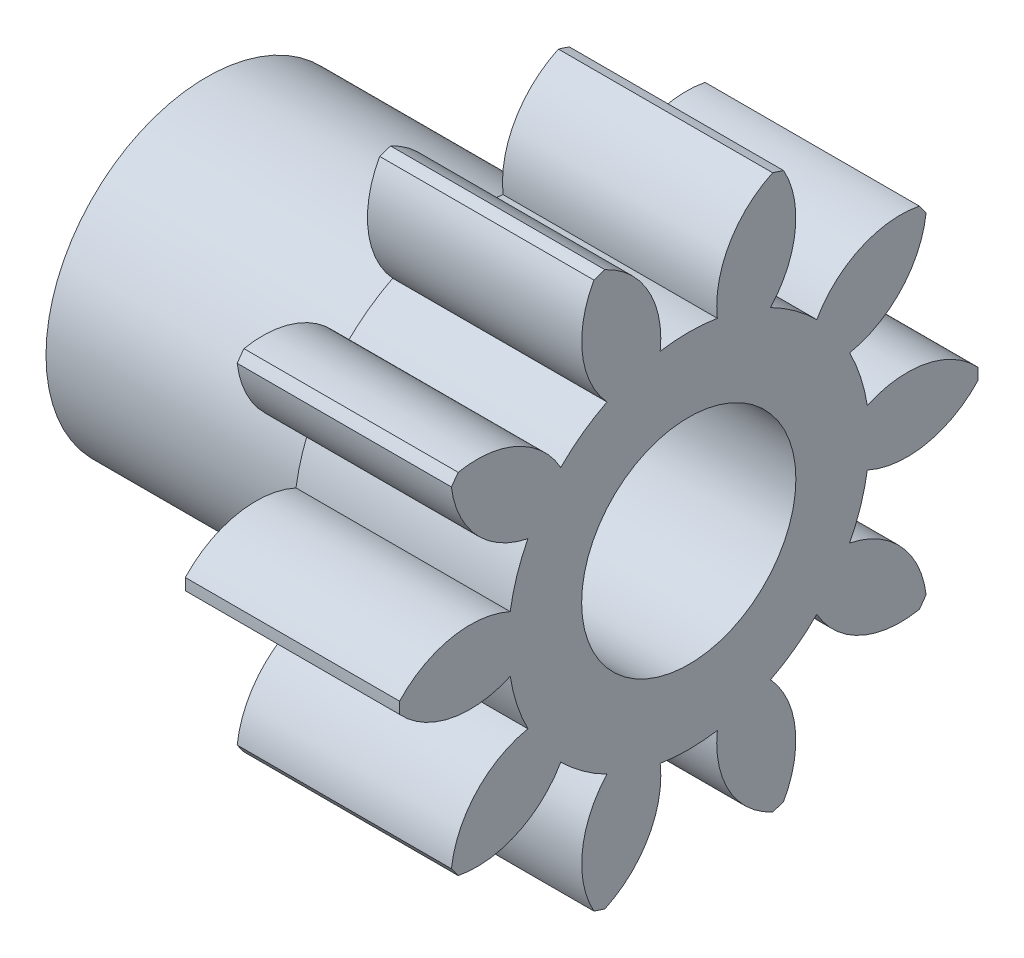
SolidWorks part; units mm, degrees
note: The reader was unsure of these and kept them because the rebuilt part matched: shared geometry of "Sketch8<2>".
ref_plane "Plane1" through (0, 0, 0) normal (0, 0, 1) x (1, 0, 0)
ref_plane "Plane2" through (0, 0, 0) normal (0, 1, 0) x (1, 0, 0)
ref_plane "Plane3" through (0, 0, 0) normal (1, 0, 0) x (0, 0, -1)
sketch "HoldingSke" plane through (0, 0, 0) normal (0, 1, 0) x (1, 0, 0)
  line L0 (0, 0) -> (1.0942, -0.1929)
  line L1 (-15, 0) -> (100, 0) construction
  line L2 (0, 0) -> (-2.1039, 2.3779)
  line L3 (0, 0) -> (-11.863, 4.5341)
  line L4 (0, 0) -> (8.5048, 1.4996)
  line L5 (0, 0) -> (-8.4326, -3.1451)
  line L6 (0, 0) -> (-3.3159, -2.2372)
  line L7 (-2.1039, 2.3779) -> (-0.1666, 11.167)
  line L8 (-76.2, 54.61) -> (-75.5, 54.61)
  line L9 (-71.009, 38.7566) -> (-53.1078, 45.2721)
  line L10 (-76.2, 71.12) -> (104.1128, 71.12)
  line L11 (0, 0) -> (-4, 0)
  line L12 (-76.2, 101.6) -> (-76.166, 101.6)
  line L13 (24.9733, 27.94) -> (52.9518, 28.4284)
  line L14 (24.9733, 27.94) -> (24.9743, 27.94)
  line L15 (24.9733, 27.94) -> (100.4006, 29.5858)
  line L16 (-63.627, -0.9) -> (-12.827, -0.9)
  circle A0 centre (0, 0) radius 2
  circle A1 centre (0, 0) radius 3
  circle A2 centre (0, 0) radius 3
  circle A3 centre (0, 0) radius 2
  dimension "MHD" = 6
  dimension "Hub_dia" = 6
  dimension "Bore" = 4
  dimension "MBD" = 4
  dimension "Num_teeth" = 10
  dimension "Pitch_radius" = 180.3128
  dimension "Pitch" = 1.1111
  dimension "Width" = 4
  dimension "Overall_len" = 9
  dimension "Show_teeth" = 10
  dimension "Thickness" = 4
  dimension "OAL" = 9.0001
  dimension "T_dim" = 0.7
  dimension "Ap" = 20
  dimension "H" = 19.05
  dimension "Backlash" = 0.034
  dimension "Addendum_fac" = 1
  dimension "Dedendum_fac" = 1.25
  dimension "Clearance_fac" = 0.25
  dimension "Dedendum_add" = 0.001
  dimension "Module" = 0.9
sketch "BasProSke" plane through (0, 0, 0) normal (0, 1, 0) x (1, 0, 0)
  line L0 (-10, 0) -> (60, 0) construction
  line L1 (0, 0) -> (0, 5.4)
  line L2 (0, 0) -> (4, 0)
  line L3 (4, 0) -> (4, 5.4)
  line L4 (4, 5.4) -> (0, 5.4)
  dimension "Diameter" = 10.8
  dimension "Thickness" = 4
revolve "Base-Revolve" add sketch "BasProSke" angle 360 about L0
sketch "TooCutSke" plane through (0, 0, 0) normal (1, 0, 0) x (0, 0, -1)
  line L1 (0, 0) -> (0, 107) construction
  line L2 (0, 0) -> (-0.7633, 4.4348) construction
  line L3 (0, 0) -> (-2.7525, 8.4713) construction
  line L4 (-0.7633, 4.4348) -> (-1.3762, 4.2356) construction
  arc A0 (0.5333, 3.3316) -> (-0.5333, 3.3316) centre (0, 0) ccw
  arc A1 (1.6013, 5.1837) -> (-1.6013, 5.1837) centre (0, 0) ccw
  circle A2 centre (0, 0) radius 4.5 construction
  circle A3 centre (0, 0) radius 4.2286 construction
  arc A4 (-0.5333, 3.3316) -> (-1.6013, 5.1837) centre (-2.3218, 3.5342) ccw
  arc A5 (1.6013, 5.1837) -> (0.5333, 3.3316) centre (2.3218, 3.5342) ccw
  dimension "Root_dia" = 6.748
  dimension "Overcut_dia" = 10.8508
  dimension "Pitch_dia" = 9
  dimension "Base_dia" = 8.4572
  dimension "Flank_rad" = 1.8
  dimension "Half_ang" = 18
  dimension "Half_CT" = 0.6445
extrude "ToothCut" cut sketch "TooCutSke" along normal through all
fillet "Breaks" [suppressed] radius 0.018
fillet "RootFillets" [suppressed] radius 0.226
pattern_circular "TeethCuts" count 10 every 36 about axis through (-10, 0, 0) along (1, 0, 0) of "ToothCut", "RootFillets", "Breaks"
sketch "HubNeaOneSke" plane through (0, 0, 0) normal (-1, 0, 0) x (0, 0, 1)
  circle A0 centre (0, 0) radius 3
  dimension "Diameter" = 6
extrude "HubNearOne" add sketch "HubNeaOneSke" along normal blind 5.0001
sketch "HubNeaBotSke" plane through (0, 0, 0) normal (-1, 0, 0) x (0, 0, 1)
  circle A0 centre (0, 0) radius 3
  dimension "Diameter" = 6
extrude "HubNearBoth" [suppressed] add sketch "HubNeaBotSke" along normal blind 2.5
ref_plane "FarPln" through (4, 0, 0) normal (1, 0, 0) x (0, 0, -1)
sketch "HubFarSke" plane through (4, 0, 0) normal (1, 0, 0) x (0, 0, -1)
  circle A0 centre (0, 0) radius 3
  dimension "Diameter" = 6
extrude "HubFar" [suppressed] add sketch "HubFarSke" along normal blind 2.5
sketch "BorSke" plane through (0, 0, 0) normal (1, 0, 0) x (0, 0, -1)
  circle A0 centre (0, 0) radius 2
  dimension "Diameter" = 4
extrude "Bore" cut sketch "BorSke" along normal mid plane 18.0001
sketch "KeySke" plane through (0, 0, 0) normal (1, 0, 0) x (0, 0, -1)
  line L0 (-0.8, 0) -> (-0.8, 2.7)
  line L1 (-0.8, 2.7) -> (0.8, 2.7)
  line L2 (0.8, 2.7) -> (0.8, 0)
  line L3 (0, 0) -> (0, 34) construction
  line L4 (-0.8, 0) -> (0.8, 0)
  dimension "Offset" = 2.7
  dimension "Width" = 1.6
extrude "Keyway" [suppressed] cut sketch "KeySke" along normal mid plane 18.0001
pattern_circular "Keyway2" [suppressed] count 2 every 90 about axis through (-10, 0, 0) along (1, 0, 0)
ref_plane "Plane4" through (0, -3, 0) normal (0, -1, 0) x (-1, 0, 0)
sketch "Sketch8" plane through (0, -3, 0) normal (0, -1, 0) x (-1, 0, 0)
  line L0 (0, -0.5333) -> (0, 0.5333) construction
  circle A0 centre (2.5, 0) radius 1.25
  point P2 (0, 0)
  dimension "D1" = 2.5
curve "Helix/Spiral1" pitch 0.5 height 3 turns 6
extrude "Cut-Extrude1" cut sketch "Sketch8<2>" against normal blind 2
sketch "Sketch8<2>" plane through (0, -3, 0) normal (0, -1, 0) x (-1, 0, 0) same geometry as "Sketch8"
sketch "Sketch10" plane through (0, 0, 0) normal (0, 0, 1) x (1, 0, 0)
  line L0 (-3.75, -3) -> (-3.75, -0.8273) construction
  line L2 (-3.75, -2.8728) -> (-3.925, -2.9739)
  line L3 (-3.925, -3.0605) -> (-3.75, -3.1615)
  line L4 (-3.75, -3.1615) -> (-3.75, -2.8728)
  circle A0 centre (-3.8333, -3.0172) radius 0.0833 construction
  arc A1 (-3.925, -2.9739) -> (-3.925, -3.0605) centre (-3.9, -3.0172) ccw
  point P10 (-4, -3.0172)
  dimension "D2" = 0.05
  dimension "D1" = 0.25
sweep "Cut-Sweep1" cut profiles "Sketch10" path "Helix/Spiral1"
equation "' \"Module@HoldingSke\" = 6.35"
equation "' \"Num_teeth@HoldingSke\" = 12"
equation "' \"Ap@HoldingSke\" =  20"
equation "' \"Width@HoldingSke\" = 0.5 * 25.4"
equation "' \"Hub_dia@HoldingSke\"= 1 * 25.4"
equation "' \"Overall_len@HoldingSke\" = 1.0 * 25.4"
equation "' \"Bore@HoldingSke\" = 0.75 * 25.4"
equation "' \"T_dim@HoldingSke\" = 0.1 * 25.4"
equation "' \"Width@KeySke\" = 0.25 * 25.4"
equation "' \"Show_teeth@HoldingSke\" = 13"
equation "' \"Backlash@HoldingSke\" = 0.009 * 25.4"
equation "' \"Addendum_fac@HoldingSke\" = 1.0"
equation "' \"Dedendum_fac@HoldingSke\" = 1.25"
equation "' \"Dedendum_add@HoldingSke\" = 0.00005 * 25.4"
equation "' \"Clearance_fac@HoldingSke\" = 0.25"
equation "\"Pitch@HoldingSke\" = 1 / \"Module@HoldingSke\""
equation "\"Overcut_dia@TooCutSke\" = (\"Num_teeth@HoldingSke\" + 2 * \"Addendum_fac@HoldingSke\") / \"Pitch@HoldingSke\" + 0.002 * 25.4"
equation "\"Pitch_dia@TooCutSke\" = \"Num_teeth@HoldingSke\" / \"Pitch@HoldingSke\""
equation "\"Base_dia@TooCutSke\" = \"Num_teeth@HoldingSke\" / \"Pitch@HoldingSke\" * cos((\"Ap@HoldingSke\"  * 3.14159265 / 180))"
equation "\"Root_dia@TooCutSke\" = (\"Num_teeth@HoldingSke\" + 2) / \"Pitch@HoldingSke\" - 2 * (\"Addendum_fac@HoldingSke\" + \"Dedendum_fac@HoldingSke\") / \"Pitch@HoldingSke\" - \"Dedendum_add@HoldingSke\" * 2"
equation "\"Half_ang@TooCutSke\" = 180 / \"Num_teeth@HoldingSke\""
equation "\"Half_CT@TooCutSke\" = \"Num_teeth@HoldingSke\" / \"Pitch@HoldingSke\" * sin((3.14159265 / 2 / \"Num_teeth@HoldingSke\")) / 2 - 7 * \"Backlash@HoldingSke\" / 4"
equation "\"Flank_rad@TooCutSke\" = \"Num_teeth@HoldingSke\" / \"Pitch@HoldingSke\" / 5"
equation "\"Radius@RootFillets\" = \"Clearance_fac@HoldingSke\" / \"Pitch@HoldingSke\" + \"Dedendum_add@HoldingSke\""
equation "\"Break_rad@Breaks\" = 0.02 / \"Pitch@HoldingSke\""
equation "\"Thickness@HoldingSke\" = \"Width@HoldingSke\""
equation "\"OAL@HoldingSke\" = \"Thickness@HoldingSke\""
equation "\"MHD@HoldingSke\" = (\"Num_teeth@HoldingSke\" + 2) / \"Pitch@HoldingSke\" - 2 * (\"Addendum_fac@HoldingSke\" + \"Dedendum_fac@HoldingSke\")  / \"Pitch@HoldingSke\" - \"Dedendum_add@HoldingSke\" * 2"
equation "\"MBD@HoldingSke\" = (\"Num_teeth@HoldingSke\" + 2) / \"Pitch@HoldingSke\" - 2 * (\"Addendum_fac@HoldingSke\" + \"Dedendum_fac@HoldingSke\")  / \"Pitch@HoldingSke\" - \"Dedendum_add@HoldingSke\" * 2 - 0.002 * 25.4"
equation "\"MHD@HoldingSke\" = ((sgn( \"MHD@HoldingSke\" - \"Hub_dia@HoldingSke\" )-1)*( \"MHD@HoldingSke\" - \"Hub_dia@HoldingSke\" ))/-2+ \"Hub_dia@HoldingSke\""
equation "\"MBD@HoldingSke\" = ((sgn( \"MBD@HoldingSke\" - \"Bore@HoldingSke\" )-1)*( \"MBD@HoldingSke\" - \"Bore@HoldingSke\" ))/-2+ \"Bore@HoldingSke\""
equation "\"OAL@HoldingSke\" = ((sgn( \"OAL@HoldingSke\" - \"Overall_len@HoldingSke\" )+1)*( \"OAL@HoldingSke\" - \"Overall_len@HoldingSke\" ))/2 + \"Overall_len@HoldingSke\" + 0.000002 * 25.4"
equation "\"Num_teeth@TeethCuts\" = int( \"Show_teeth@HoldingSke\" ) + 1"
equation "\"Num_teeth@TeethCuts\" = ((sgn( \"Num_teeth@TeethCuts\" - \"Num_teeth@HoldingSke\" )-1)*( \"Num_teeth@TeethCuts\" - \"Num_teeth@HoldingSke\" ))/-2+ \"Num_teeth@HoldingSke\""
equation "\"Num_teeth@TeethCuts\" = ((sgn( \"Num_teeth@TeethCuts\" - 2.0)+1)*( \"Num_teeth@TeethCuts\" - 2.0))/2 +2.0"
equation "\"Angle@TeethCuts\" = 360.0 / \"Num_teeth@HoldingSke\""
equation "\"Diameter@BasProSke\" = (\"Num_teeth@HoldingSke\" + 2 * \"Addendum_fac@HoldingSke\") / \"Pitch@HoldingSke\""
equation "\"Thickness@BasProSke\"  = \"Thickness@HoldingSke\""
equation "' \"Fillet_rad@BasProSke\" =  \"Thickness@HoldingSke\" * 0.05"
equation "\"MHD@HoldingSke\" = ((sgn( \"MHD@HoldingSke\" - \"Root_dia@TooCutSke\" )-1)*( \"MHD@HoldingSke\" - \"Root_dia@TooCutSke\" ))/-2+ \"Root_dia@TooCutSke\""
equation "\"Diameter@HubNeaOneSke\" = \"MHD@HoldingSke\""
equation "\"Length@HubNearOne\" = \"OAL@HoldingSke\" - \"Thickness@BasProSke\""
equation "\"Diameter@HubNeaBotSke\" = \"MHD@HoldingSke\""
equation "\"Length@HubNearBoth\" = ( \"OAL@HoldingSke\" - \"Thickness@BasProSke\" ) / 2.0"
equation "\"Thickness@FarPln\" = \"Thickness@BasProSke\""
equation "\"Diameter@HubFarSke\" = \"MHD@HoldingSke\""
equation "\"Length@HubFar\" = ( \"OAL@HoldingSke\" - \"Thickness@BasProSke\" ) / 2.0"
equation "\"Diameter@BorSke\" = \"MBD@HoldingSke\""
equation "\"D1@Bore\" = \"OAL@HoldingSke\" * 2.0"
equation "\"D1@Keyway\" = \"OAL@HoldingSke\" * 2.0"
equation "\"Offset@KeySke\" = \"T_dim@HoldingSke\" + \"MBD@HoldingSke\" / 2.0"
